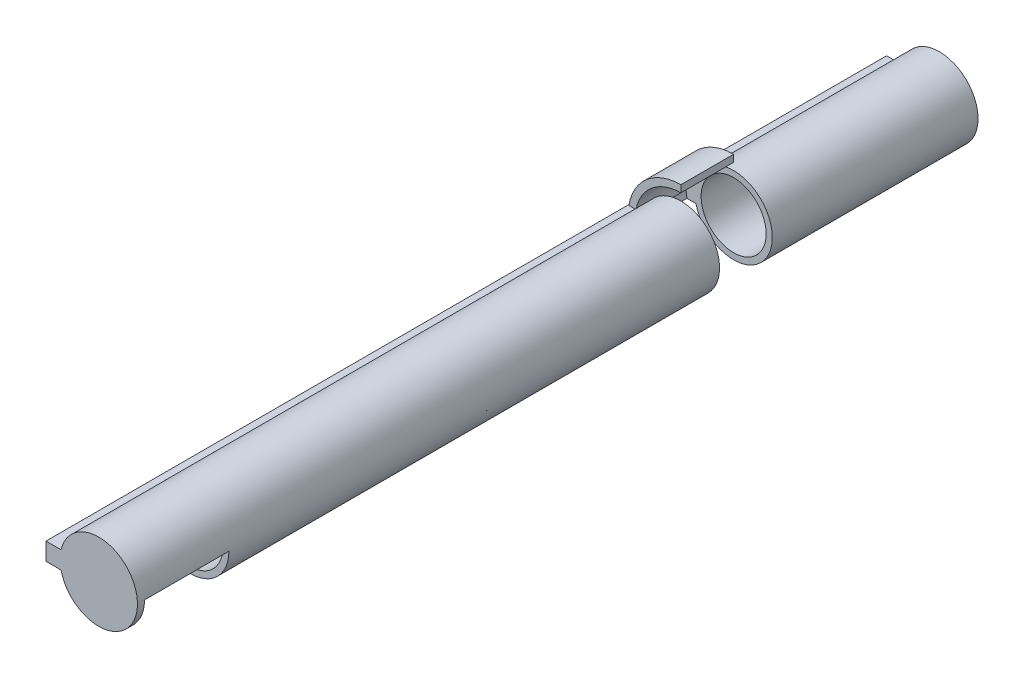
SolidWorks part; units mm, degrees
material "Manual Density from Real Component Plastica Fusoliera"
ref_plane "Piano frontale" through (0, 0, 0) normal (0, 0, 1) x (1, 0, 0)
ref_plane "Piano superiore" through (0, 0, 0) normal (0, 1, 0) x (1, 0, 0)
ref_plane "Piano destro" through (0, 0, 0) normal (1, 0, 0) x (0, 0, -1)
sketch "Schizzo1" plane through (0, 0, 0) normal (0, 0, 1) x (1, 0, 0)
  circle A0 centre (0, 0) radius 11
  circle A1 centre (0, 0) radius 9.25
  dimension "D1" = 22
  dimension "D2" = 18.5
extrude "Tubo" add sketch "Schizzo1" along normal blind 210
sketch "Schizzo2" plane through (0, 0, 210) normal (0, 0, 1) x (1, 0, 0)
  line L0 (0, -9.25) -> (0, -11)
  line L1 (9.25, 0) -> (11, 0)
  arc A0 (11, 0) -> (0, -11) centre (0, 0) ccw
  arc A2 (0, -9.25) -> (9.25, 0) centre (0, 0) cw
  circle A4 centre (0, 0) radius 9.25 construction
  circle A5 centre (0, 0) radius 11 construction
extrude "IngressoCavi" add sketch "Schizzo2" along normal blind 27
sketch "Schizzo4" plane through (0, 0, 210) normal (0, 0, 1) x (1, 0, 0)
  circle A0 centre (0, 0) radius 11
  circle A1 centre (0, 0) radius 6.5
  dimension "D1" = 22
  dimension "D2" = 13
extrude "FondoCorsa" add sketch "Schizzo4" along normal blind 3
sketch "Schizzo5" plane through (0, 0, 237) normal (0, 0, 1) x (1, 0, 0)
  circle A0 centre (0, 0) radius 11
  arc A1 (11, 0) -> (0, -11) centre (0, 0) ccw construction
extrude "Tappo" add sketch "Schizzo5" along normal blind 2
sketch "Schizzo6" plane through (0, 0, 0) normal (0, 0, 1) x (1, 0, 0)
  line L0 (-11, 2.5) -> (-15, 2.5)
  line L1 (-11, 2.5) -> (-10.7121, 2.5)
  line L2 (-11, 2.5) -> (-11, -2.5) construction
  line L3 (-11, -2.5) -> (-10.7121, -2.5)
  line L4 (-10.7121, 2.5) -> (-10.7121, -2.5)
  line L5 (-15, 2.5) -> (-15, -2.5)
  line L6 (-15, -2.5) -> (-11, -2.5)
  circle A0 centre (0, 0) radius 11 construction
  point P8 (-11, 0)
  dimension "D1" = 5
  dimension "D2" = 4
extrude "BaseInferiore" add sketch "Schizzo6" along normal up to surface (239 mm away) up to face at (11, 0, 239)
ref_plane "PianoFineAnello" through (0, 0, 73.5) normal (0, 0, 1) x (1, 0, 0)
sketch "Schizzo7" plane through (0, 0, 73.5) normal (0, 0, 1) x (1, 0, 0)
  circle A0 centre (0, 0) radius 13.5
  dimension "D1" = 27
extrude "TaglioAnello" cut sketch "Schizzo7" against normal blind 15
sketch "Schizzo8" plane through (0, 0, 73.5) normal (0, 0, 1) x (1, 0, 0)
  line L0 (-15, 2.5) -> (-15, -2.5) construction
  line L1 (0, 15) -> (0, 13)
  line L2 (-15, 0) -> (-13, 0)
  arc A1 (-13, 0) -> (0, 13) centre (0, 0) cw
  arc A2 (-15, 0) -> (0, 15) centre (0, 0) cw
  dimension "D1" = 2
extrude "SupportoAnello" add sketch "Schizzo8" against normal blind 15
sketch "Schizzo9" plane through (0, 0, 210) normal (0, 0, -1) x (-1, 0, 0)
  line L0 (0, 0) -> (-9.25, 0)
  line L1 (0, 0) -> (0, -9.25)
  arc A0 (-9.25, 0) -> (0, -9.25) centre (0, 0) ccw
  circle A1 centre (0, 0) radius 9.25 construction
extrude "FacilitazioneUscitaCavi" cut sketch "Schizzo9" against normal up to surface (3 mm away) up to face at (6.5, 0, 213)
fillet "RaccordoFacilitazioneCavi" radius 8 2 edges at (6.5, 0, 211.5) (0, -6.5, 211.5)
